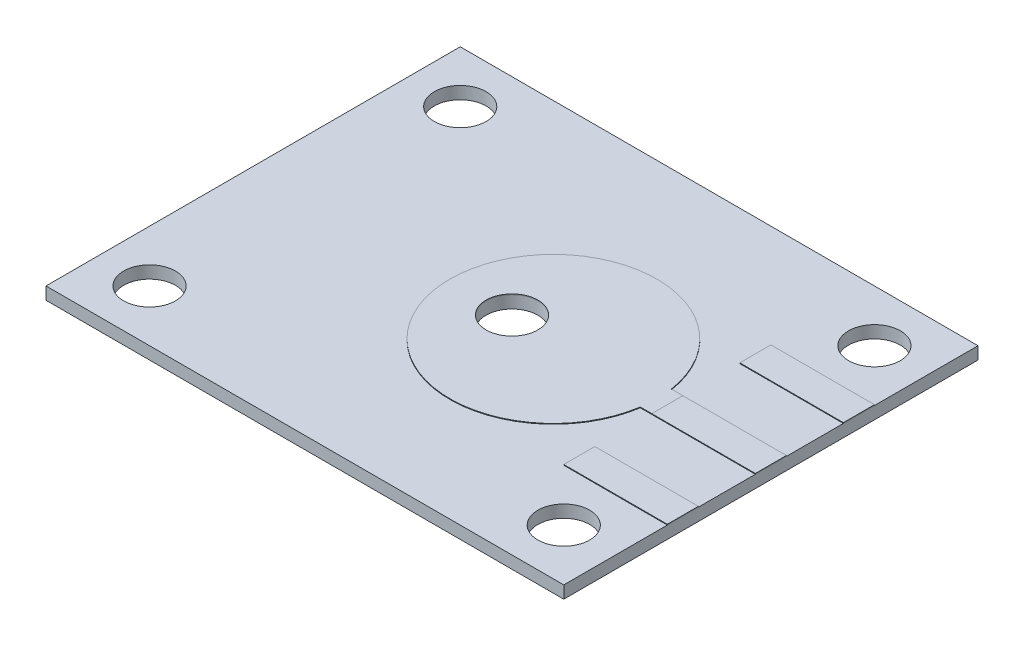
SolidWorks part; units mm, degrees
ref_plane "Front Plane" through (0, 0, 0) normal (0, 0, 1) x (1, 0, 0)
ref_plane "Top Plane" through (0, 0, 0) normal (0, 1, 0) x (1, 0, 0)
ref_plane "Right Plane" through (0, 0, 0) normal (1, 0, 0) x (0, 0, -1)
sketch "Sketch1" plane through (0, 0, 0) normal (0, 1, 0) x (1, 0, 0)
  line L1 (-12.5, -10) -> (12.5, -10)
  line L2 (-12.5, -10) -> (-12.5, 10)
  line L3 (-12.5, 10) -> (12.5, 10)
  line L4 (12.5, -10) -> (12.5, 10)
  line L5 (-12.5, -10) -> (12.5, 10) construction
  line L6 (-12.5, 10) -> (12.5, -10) construction
  point P0 (0, 0)
  dimension "D1" = 25
  dimension "D2" = 20
extrude "Boss-Extrude1" add sketch "Sketch1" along normal blind 0.6 from offset 0.635 offset against normal yes
sketch "Sketch2" plane through (0, -0.035, 0) normal (0, 1, 0) x (1, 0, 0)
  line L0 (-12.5, 10) -> (-12.5, -10) construction
  line L1 (12.5, 10) -> (-12.5, 10) construction
  line L2 (0, 10) -> (0, -10) construction
  line L3 (-12.5, -10) -> (12.5, -10) construction
  line L4 (-12.5, 0) -> (12.5, 0) construction
  line L5 (12.5, -10) -> (12.5, 10) construction
  circle A0 centre (-10, 7.5) radius 1.25
  circle A2 centre (10, 7.5) radius 1.25
  circle A3 centre (10, -7.5) radius 1.25
  circle A4 centre (-10, -7.5) radius 1.25
  circle A6 centre (0, 0) radius 1.25
  dimension "D1" = 2.5
  dimension "D2" = 2.5
  dimension "D3" = 2.5
  dimension "D4" = 2.5
extrude "Cut-Extrude1" cut sketch "Sketch2" against normal blind 0.6
sketch "Sketch9" plane through (0, -0.035, 0) normal (0, 1, 0) x (1, 0, 0)
  line L0 (0, 0) -> (12.5, 0) construction
  line L1 (12.5, -10) -> (12.5, 10) construction
  line L2 (7.5, 3.5) -> (7.5, 5)
  line L3 (7.5, -0.75) -> (12.5, -0.75)
  line L4 (7.5, -0.75) -> (7.5, 0.75)
  line L5 (7.5, 0.75) -> (12.5, 0.75)
  line L6 (12.5, -0.75) -> (12.5, 0.75)
  line L7 (7.5, -0.75) -> (12.5, 0.75) construction
  line L8 (7.5, 0.75) -> (12.5, -0.75) construction
  line L9 (7.5, 3.5) -> (12.5, 3.5)
  line L10 (12.5, 3.5) -> (12.5, 5)
  line L11 (7.5, 5) -> (12.5, 5)
  line L12 (7.5, -5) -> (7.5, -3.5)
  line L13 (7.5, -5) -> (12.5, -5)
  line L14 (12.5, -5) -> (12.5, -3.5)
  line L15 (7.5, -3.5) -> (12.5, -3.5)
  point P5 (10, 0)
  dimension "D1" = 5
  dimension "D2" = 1.5
  dimension "D4" = 2.75
  dimension "D6" = 2.75
  dimension "D3" = 2
  dimension "D5" = 2
extrude "Boss-Extrude2" add sketch "Sketch9" against normal blind 0.2 from offset 0.035 separate body
sketch "Sketch8" plane through (0, -0.035, 0) normal (0, 1, 0) x (1, 0, 0)
  line L0 (0, 0) -> (2, 0) construction
  line L2 (7, 0) -> (6.991, -0.2999)
  line L10 (7.5, 0.75) -> (6.7, 0.75)
  line L12 (7.5, 0.75) -> (7.5, -0.75)
  line L13 (7.5, -0.75) -> (6.7, -0.75)
  line L14 (6.7, 0.75) -> (6.7, -0.75)
  circle A0 centre (2, 0) radius 5
  circle M13 centre (0, 0) radius 1.25
  dimension "D2" = 10
  dimension "D1" = 2
  dimension "D3" = 0.3
  dimension "D4" = 1.5
  dimension "D5" = 0.8
extrude "Boss-Extrude3" add sketch "Sketch8" along normal blind 0.035 separate body contours L10 A0 L13 L14 M13 | L14 L13 L12 L10 region at (2.1062, -0.035, 0)
